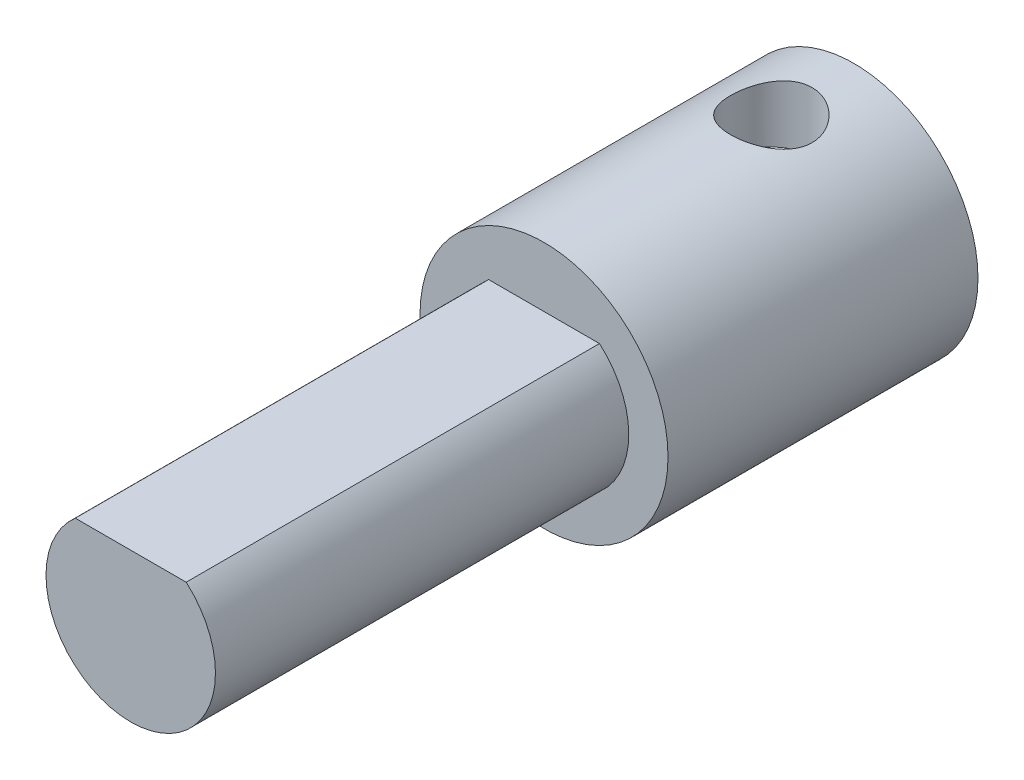
SolidWorks part; units mm, degrees
ref_plane "Front" through (0, 0, 0) normal (0, 0, 1) x (1, 0, 0)
ref_plane "Top" through (0, 0, 0) normal (0, 1, 0) x (1, 0, 0)
ref_plane "Right" through (0, 0, 0) normal (1, 0, 0) x (0, 0, -1)
sketch "Sketch1" plane through (0, 0, 0) normal (0, 0, 1) x (1, 0, 0)
  line L0 (-2.6833, 3.1) -> (2.6833, 3.1)
  circle A0 centre (0, 0) radius 4.1
  circle A1 centre (0, 0) radius 6
  dimension "D1" = 8.2
  dimension "D3" = 12
  dimension "D2" = 3.1
extrude "Boss-Extrude1" add sketch "Sketch1" along normal blind 15 contours A1 A0 | L0 A0 region at (0, 3.5045, 0) region at (-5.8303, 0, 0)
extrude "Boss-Extrude2" add sketch "Sketch1<3>" along normal blind 20 and the other way blind 5 from surface contours L0 A0 region at (0, -0.2621, 0) starting at face at (0, -0.5, 15)
sketch "Sketch1<3>" plane through (0, 0, 0) normal (0, 0, 1) x (1, 0, 0) same geometry as "Sketch1"
sketch "Sketch3" plane through (0, 0, 0) normal (0, 1, 0) x (1, 0, 0)
  circle A0 centre (0, -4) radius 1.975
  dimension "D1" = 3.95
  dimension "D2" = 4
extrude "Cut-Extrude1" cut sketch "Sketch3" along normal up to next
